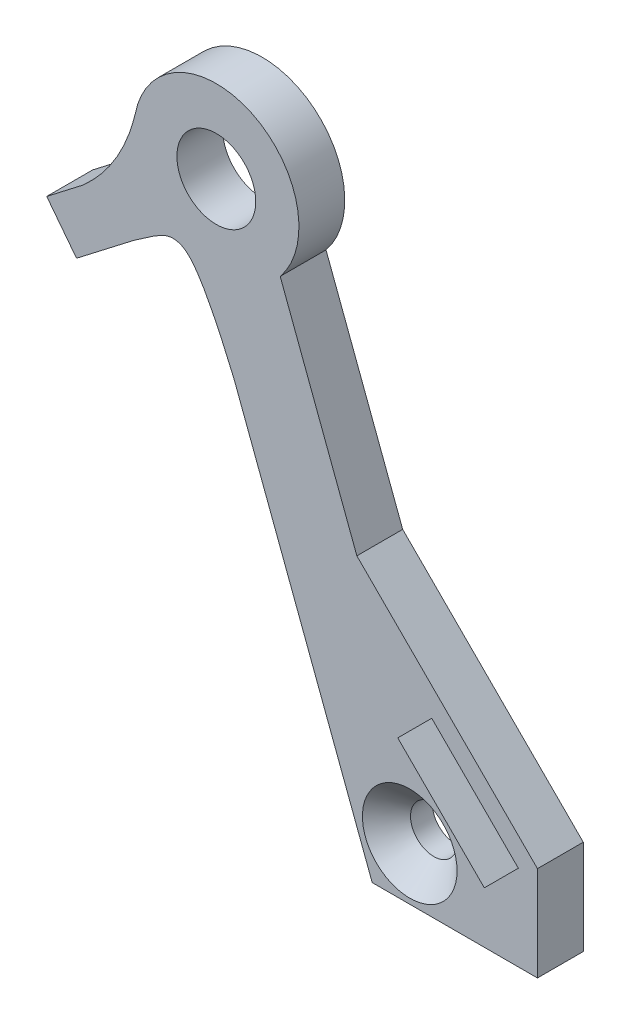
SolidWorks part; units mm, degrees
ref_plane "Front Plane" through (0, 0, 0) normal (0, 0, 1) x (1, 0, 0)
ref_plane "Top Plane" through (0, 0, 0) normal (0, 1, 0) x (1, 0, 0)
ref_plane "Right Plane" through (0, 0, 0) normal (1, 0, 0) x (0, 0, -1)
sketch "Sketch1" plane through (0, 0, 0) normal (0, 0, 1) x (1, 0, 0)
  line L0 (0, 11) -> (11, 0) construction
  line L1 (0, 0) -> (11, 0)
  line L2 (0, 0) -> (0, 11) construction
  line L3 (0, 11) -> (11, 11) construction
  line L4 (11, 0) -> (11, 11) construction
  line L5 (0, 0) -> (2.5, 0)
  line L6 (0, 0) -> (0, 3.5)
  line L7 (0, 3.5) -> (2.5, 3.5) construction
  line L8 (2.5, 0) -> (2.5, 3.5) construction
  line L9 (7.7859, 3.108) -> (7.839, 3.161) construction
  line L10 (7.4645, 3.4295) -> (1.7015, 9.1924)
  line L11 (1.7015, 9.1924) -> (3.9643, 11.4551)
  line L12 (7.4645, 3.4295) -> (9.7272, 5.6922)
  line L13 (3.9643, 11.4551) -> (9.7272, 5.6922)
  line L14 (0, 0) -> (-12.9496, 34.4032)
  line L15 (-12.9496, 34.4032) -> (-7.8021, 36.3407)
  line L16 (-7.8021, 36.3407) -> (-1.0208, 18.3247)
  line L17 (-1.0208, 18.3247) -> (11, 6.3039)
  line L18 (11, 0) -> (7.5175, 3.4825)
  line L19 (11, 6.3039) -> (11, 0)
  line L20 (0, 0) -> (0, 40.9886) construction
  line L21 (-10.3759, 35.372) -> (-20.6719, 27.4353) construction
  line L22 (-19.6799, 26.1483) -> (-21.664, 28.7223)
  line L23 (-21.664, 28.7223) -> (-15.5295, 33.451) construction
  line L24 (-19.6799, 26.1483) -> (-13.5453, 30.877)
  line L25 (-21.664, 28.7223) -> (-19.2435, 30.5881)
  line L26 (-15.7754, 36.4182) -> (-10.3759, 35.372) construction
  circle A0 centre (2.5, 3.5) radius 1.5
  circle A1 centre (-10.3759, 35.372) radius 2.625
  circle A3 centre (-10.3759, 35.372) radius 5.5
  spline S0 degree 2 poles (-19.2435, 30.5881) (-16.6298, 32.9139) (-15.7754, 36.4182) knots 0 0 0 1 1 1
  spline S1 degree 3 poles (-15.8542, 29.0973) (-14.3029, 30.1752) (-13.1708, 31.0754) (-11.3978, 29.6078) (-9.212, 24.4735) knots 0 0 0 0 0.517104 1 1 1 1
  point P28 (-20.6719, 27.4353)
  point P35 (-5.3889, 31.8587)
  point P37 (-5.4122, 33.003)
  point P38 (-5.6911, 31.9182)
  dimension "D5" = 3
  dimension "D6" = 5.25
  dimension "D7" = 11
  dimension "D26" = 6.892
  dimension "D1" = 11
  dimension "D2" = 11
  dimension "D3" = 3.5
  dimension "D4" = 2.5
  dimension "D8" = 45
  dimension "D9" = 6.3039
  dimension "D10" = 90
  dimension "D11" = 90
  dimension "D12" = 19.25
  dimension "D13" = 17
  dimension "D14" = 3.2
  dimension "D15" = 8.15
  dimension "D16" = 0.075
  dimension "D17" = 4.925
  dimension "D18" = 5.5
  dimension "D19" = 90
  dimension "D20" = 3.25
  dimension "D21" = 90
  dimension "D22" = 90
  dimension "D23" = 13
  dimension "D24" = 73
  dimension "D25" = 3.0562
  dimension "D27" = 31.593
extrude "Boss-Extrude1" add sketch "Sketch1" along normal blind 3.05 contours A3 S1 L14 L15 A1 L16 S0 | L14 A3 L16 L15 A1 | A3 L14 L1 L12 L10 L11 L13 L19 L17 L16 A0 | S0 L25 L22 L24 A3 | L24 S1 A3 | A3 S1 L14 region at (-0.642, 13.4599, 0) region at (-11.0161, 28.5794, 0) region at (-11.9493, 30.2638, 0) region at (-9.1274, 32.0551, 0) region at (-13.9319, 30.3797, 0) region at (-17.5536, 30.1501, 0)
hole_wizard "CSK for M3 Flat Head Machine Screw1" positions "Sketch2" profile "Sketch3" countersink size "M3" standard "ANSI Metric" end condition through all
sketch "Sketch2" plane through (0, 0, 3.05) normal (0, 0, 1) x (1, 0, 0)
  point P0 (2.5, 3.5)
sketch "Sketch3" plane through (2.5, 3.5, 3.05) normal (1, 0, 0) x (0, -1, 0)
  line L0 (0, 0) -> (0, 3.05)
  line L1 (0, 3.05) -> (1.55, 3.05)
  line L2 (1.55, 3.05) -> (1.55, 1.6)
  line L3 (1.55, 1.6) -> (3.15, 0)
  line L5 (3.15, 0) -> (0, 0)
  line L6 (-1.55, 1.6) -> (-3.15, 0) construction
  line L11 (0, -6.35) -> (0, 107.95) construction
  dimension "Thru Hole Dia." = 3.1
  dimension "Thru Hole Depth" = 3.05
  dimension "Near C'Sink Dia." = 6.3
  dimension "Near C'Sink Angle" = 90
